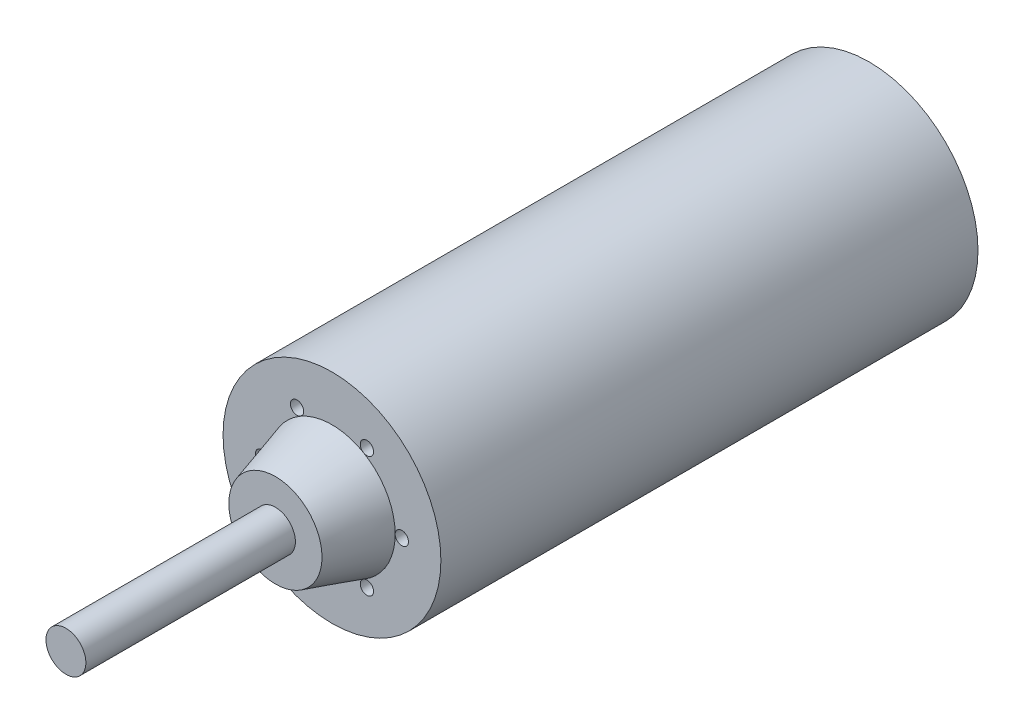
SolidWorks part; units mm, degrees
ref_plane "Front Plane" through (0, 0, 0) normal (0, 0, 1) x (1, 0, 0)
ref_plane "Top Plane" through (0, 0, 0) normal (0, 1, 0) x (1, 0, 0)
ref_plane "Right Plane" through (0, 0, 0) normal (1, 0, 0) x (0, 0, -1)
sketch "Sketch1" plane through (0, 0, 0) normal (0, 0, 1) x (1, 0, 0)
  circle A0 centre (0, 0) radius 32.75
  dimension "D1" = 65.5
extrude "Boss-Extrude1" add sketch "Sketch1" against normal mid plane 161.5
sketch "Sketch10" plane through (0, 0, 0) normal (1, 0, 0) x (0, 0, -1)
  line L0 (-97.75, 0) -> (-97.75, 14)
  line L1 (-80.75, 19) -> (-97.75, 14)
  line L2 (-1000, 0) -> (49000, 0) construction
  line L3 (-97.75, 0) -> (-80.75, 0)
  line L4 (-80.75, 0) -> (-80.75, 19)
  line L6 (-80.75, 32.75) -> (-80.75, -32.75) construction
  point P3 (-97.75, 0)
  dimension "D1" = 14
  dimension "D2" = 17
  dimension "D3" = 19
revolve "Revolve1" add sketch "Sketch10" angle 360 about L2
sketch "Sketch12" plane through (0, 0, 97.75) normal (0, 0, 1) x (1, 0, 0)
  circle A0 centre (0, 0) radius 6
  dimension "D1" = 12
extrude "Boss-Extrude5" add sketch "Sketch12" along normal blind 63
sketch "Sketch13" plane through (0, 0, 80.75) normal (0, 0, 1) x (1, 0, 0)
  circle A0 centre (21, 0) radius 2
  dimension "D2" = 4
  dimension "D1" = 21
extrude "Cut-Extrude1" cut sketch "Sketch13" against normal blind 10
pattern_circular "CirPattern1" count 6 over 360 about axis through (0, 0, 97.75) along (0, 0, 1) of "Cut-Extrude1"
sketch "Sketch14" plane through (0, 0, -80.75) normal (0, 0, -1) x (-1, 0, 0)
  circle A0 centre (21, 0) radius 2.5
  dimension "D2" = 5
  dimension "D1" = 21
extrude "Cut-Extrude2" cut sketch "Sketch14" against normal blind 10
pattern_circular "CirPattern2" count 4 over 360 about axis through (0, 0, -80.75) along (0, 0, 1) of "Cut-Extrude2"
